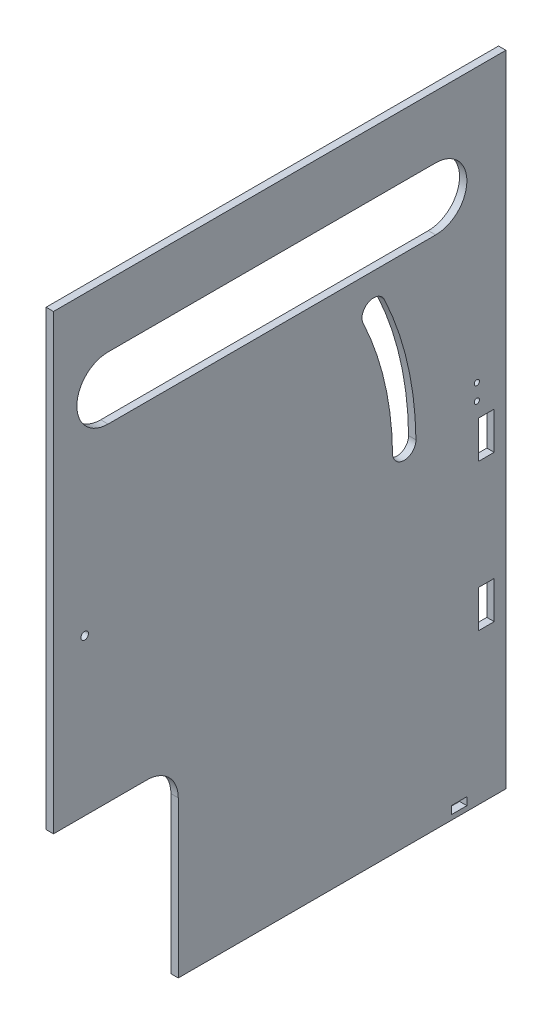
SolidWorks part; units mm, degrees
material "Acrylic (Medium-high impact)"
ref_plane "Front" through (0, 0, 0) normal (0, 0, 1) x (1, 0, 0)
ref_plane "Top" through (0, 0, 0) normal (0, 1, 0) x (1, 0, 0)
ref_plane "Right" through (0, 0, 0) normal (1, 0, 0) x (0, 0, -1)
sketch "Sketch1" plane through (0, 0, 0) normal (1, 0, 0) x (0, 0, -1)
  line L1 (-92.075, 130.175) -> (92.075, 130.175)
  line L2 (-92.075, 130.175) -> (-92.075, -130.175)
  line L3 (-92.075, -130.175) -> (92.075, -130.175)
  line L4 (92.075, 130.175) -> (92.075, -130.175)
  point P4 (-92.075, 0)
  point P6 (0, 130.175)
  dimension "D1" = 260.35
  dimension "D2" = 184.15
extrude "Boss-Extrude1" add sketch "Sketch1" along normal blind 2.9972
sketch "Sketch3" plane through (0, 0, 0) normal (-1, 0, 0) x (0, 0, 1)
  line L0 (-63.5, 104.775) -> (69.85, 104.775)
  line L1 (69.85, 79.375) -> (-63.5, 79.375)
  line L2 (-34.925, 130.175) -> (-34.925, -130.175) construction
  line L3 (-92.075, 130.175) -> (92.075, 130.175) construction
  line L4 (92.075, -130.175) -> (-92.075, -130.175) construction
  line L5 (92.075, 130.175) -> (92.075, -130.175) construction
  line L6 (-68.675, 79.375) -> (-68.675, 80.4772)
  line L12 (-63.5, 92.075) -> (-76.2, 92.075) construction
  arc A0 (69.85, 104.775) -> (69.85, 79.375) centre (69.85, 92.075) cw
  arc A1 (-63.5, 79.375) -> (-63.5, 104.775) centre (-63.5, 92.075) cw
  point P15 (82.55, 92.075)
  dimension "D1" = 25.4
  dimension "D3" = 133.35
  dimension "D2" = 9.525
  dimension "D4" = 127
  dimension "D5" = 222.25
  dimension "D8" = 5.175
extrude "Cut-Extrude1" cut sketch "Sketch3" against normal through all contours A1 L1 A0 L0 region at (0, 92.075, 3.175)
sketch "Sketch6" plane through (2.9972, 0, 0) normal (1, 0, 0) x (0, 0, -1)
  line L0 (125.525, -88.265) -> (125.525, -83.185)
  line L1 (147.525, -83.185) -> (147.525, -88.265)
  line L2 (119.525, -103.765) -> (119.525, -98.685)
  line L3 (122.525, -103.765) -> (122.525, -98.685)
  line L4 (119.525, -72.765) -> (119.525, -67.685)
  line L5 (122.525, -72.765) -> (122.525, -67.685)
  line L6 (136.525, -83.185) -> (136.525, -88.265) construction
  line L7 (153.525, -103.765) -> (153.525, -98.685)
  line L8 (150.525, -103.765) -> (150.525, -98.685)
  line L9 (150.525, -72.765) -> (150.525, -67.685)
  line L10 (153.525, -72.765) -> (153.525, -67.685)
  line L11 (-92.075, 130.175) -> (-92.075, -130.175) construction
  line L12 (-92.075, -130.175) -> (92.075, -130.175) construction
  arc A0 (125.525, -88.265) -> (147.525, -88.265) centre (136.525, -88.265) ccw
  arc A1 (147.525, -83.185) -> (125.525, -83.185) centre (136.525, -83.185) ccw
  arc A2 (119.525, -103.765) -> (122.525, -103.765) centre (121.025, -103.765) ccw
  arc A3 (122.525, -98.685) -> (119.525, -98.685) centre (121.025, -98.685) ccw
  arc A4 (119.525, -72.765) -> (122.525, -72.765) centre (121.025, -72.765) ccw
  arc A5 (122.525, -67.685) -> (119.525, -67.685) centre (121.025, -67.685) ccw
  arc A6 (153.525, -103.765) -> (150.525, -103.765) centre (152.025, -103.765) cw
  arc A7 (150.525, -98.685) -> (153.525, -98.685) centre (152.025, -98.685) cw
  arc A8 (153.525, -72.765) -> (150.525, -72.765) centre (152.025, -72.765) cw
  arc A9 (150.525, -67.685) -> (153.525, -67.685) centre (152.025, -67.685) cw
  circle A10 centre (121.025, -69.36) radius 3.175
  circle A11 centre (152.025, -69.36) radius 3.175
  circle A12 centre (121.025, -102.09) radius 3.175
  circle A13 centre (152.025, -102.09) radius 3.175
  point P37 (136.525, -85.725)
  point P38 (147.525, -85.725)
  dimension "D5" = 1.5
  dimension "D9" = 1.5
  dimension "D12" = 6.35
  dimension "D1" = 5.08
  dimension "D2" = 5.08
  dimension "D3" = 15.5
  dimension "D4" = 15.5
  dimension "D6" = 15.5
  dimension "D7" = 15.5
  dimension "D8" = 5.08
  dimension "D10" = 228.6
  dimension "D11" = 44.45
sketch "Sketch8" plane through (0, 0, 0) normal (-1, 0, 0) x (0, 0, 1)
  line L0 (92.075, 130.175) -> (92.075, -130.175) construction
  line L1 (92.075, -130.175) -> (-92.075, -130.175) construction
  line L3 (92.075, -130.175) -> (-92.075, -130.175) construction
  circle A0 centre (79.375, 9.525) radius 1.55
  circle A5 centre (-80.255, 18.925) radius 1.05
  circle A6 centre (-80.255, 12.425) radius 1.05
  point P11 (-71.755, 22.225)
  dimension "D1" = 3.1
  dimension "D15" = 3.3
  dimension "D8" = 2.1
  dimension "D2" = 12.7
  dimension "D3" = 139.7
  dimension "D6" = 151.13
  dimension "D7" = 152.4
  dimension "D9" = 6.5
  dimension "D12" = 8.5
extrude "Cut-Extrude7" cut sketch "Sketch8" against normal through all
sketch "Sketch9" plane through (0, 0, 0) normal (-1, 0, 0) x (0, 0, 1)
  line L0 (92.075, 130.175) -> (92.075, -130.175) construction
  line L1 (92.075, -53.975) -> (41.275, -53.975)
  line L2 (92.075, -53.975) -> (92.075, -130.175)
  line L3 (92.075, -130.175) -> (41.275, -130.175)
  line L4 (41.275, -53.975) -> (41.275, -130.175)
  line L5 (92.075, -130.175) -> (-92.075, -130.175) construction
  dimension "D1" = 50.8
  dimension "D2" = 76.2
extrude "Cut-Extrude8" cut sketch "Sketch9" against normal through all
fillet "Fillet1" radius 12.7 1 edges at (1.4986, -53.975, 41.275)
sketch "Sketch10" plane through (0, 0, 0) normal (-1, 0, 0) x (0, 0, 1)
  line L4 (-50.7607, -130.175) -> (-50.7607, 6.325) construction
  line L5 (41.275, -130.175) -> (-92.075, -130.175) construction
  arc A9 (-36.2288, 69.3688) -> (-50.7607, 6.325) centre (79.375, 9.525) ccw construction
  arc A10 (-42.5687, 67.0954) -> (-55.4656, 11.1443) centre (79.375, 9.525) ccw
  arc A11 (-33.9554, 63.0289) -> (-45.9413, 11.03) centre (79.375, 9.525) ccw
  arc A12 (-55.4656, 11.1443) -> (-45.9413, 11.03) centre (-50.7035, 11.0872) ccw
  arc A13 (-42.5687, 67.0954) -> (-33.9554, 63.0289) centre (-38.262, 65.0622) cw
  circle A14 centre (79.375, 9.525) radius 125.3254 construction
  circle A15 centre (79.375, 9.525) radius 130.175 construction
  circle A16 centre (79.375, 9.525) radius 134.8504 construction
  point P23 (-36.2288, 69.3688)
  dimension "D1" = 4.7625
  dimension "D2" = 136.5
  dimension "D4" = 260.35
  dimension "D3" = 53.975
extrude "Cut-Extrude9" cut sketch "Sketch10" against normal through all
sketch "Sketch14" plane through (2.9972, 0, 0) normal (1, 0, 0) x (0, 0, -1)
  line L0 (44.45, -130.175) -> (44.45, 130.175) construction
  line L5 (-41.275, -130.175) -> (92.075, -130.175) construction
  line L6 (92.075, 130.175) -> (-92.075, 130.175) construction
  line L7 (-92.075, 130.175) -> (-92.075, -53.975) construction
  line L9 (69.85, -125) -> (76.2, -125)
  line L10 (69.85, -125) -> (69.85, -128.175)
  line L11 (69.85, -128.175) -> (76.2, -128.175)
  line L12 (76.2, -125) -> (76.2, -128.175)
  circle A0 centre (-79.375, 9.525) radius 181.0945 construction
  arc A1 (35.0388, -128.905) -> (41.3847, -122.7825) centre (35.0388, -122.555) ccw construction
  dimension "D1" = 136.525
  dimension "D2" = 6.35
  dimension "D3" = 2
  dimension "D4" = 3.175
  dimension "D5" = 25.4
extrude "Cut-Extrude11" cut sketch "Sketch14" against normal through all
sketch "Sketch15" plane through (2.9972, 0, 0) normal (1, 0, 0) x (0, 0, -1)
  line L1 (80.9625, 6.075) -> (87.3125, 6.075)
  line L2 (80.9625, 6.075) -> (80.9625, -9.165)
  line L3 (80.9625, -9.165) -> (87.3125, -9.165)
  line L4 (87.3125, 6.075) -> (87.3125, -9.165)
  line L10 (92.075, -130.175) -> (92.075, 130.175) construction
  line L11 (80.9625, -53.615) -> (87.3125, -53.615)
  line L12 (80.9625, -53.615) -> (80.9625, -68.855)
  line L13 (80.9625, -68.855) -> (87.3125, -68.855)
  line L14 (87.3125, -53.615) -> (87.3125, -68.855)
  circle A0 centre (80.255, 12.425) radius 1.05 construction
  dimension "D1" = 6.35
  dimension "D2" = 15.24
  dimension "D3" = 44.45
  dimension "D4" = 4.7625
  dimension "D5" = 6.35
extrude "Cut-Extrude12" cut sketch "Sketch15" against normal through all
equation "\"bottomThickness\"= .220in"
equation "\"wallThickness\"= .118in"
equation "\"D1@Boss-Extrude1\"=\"wallThickness\""
